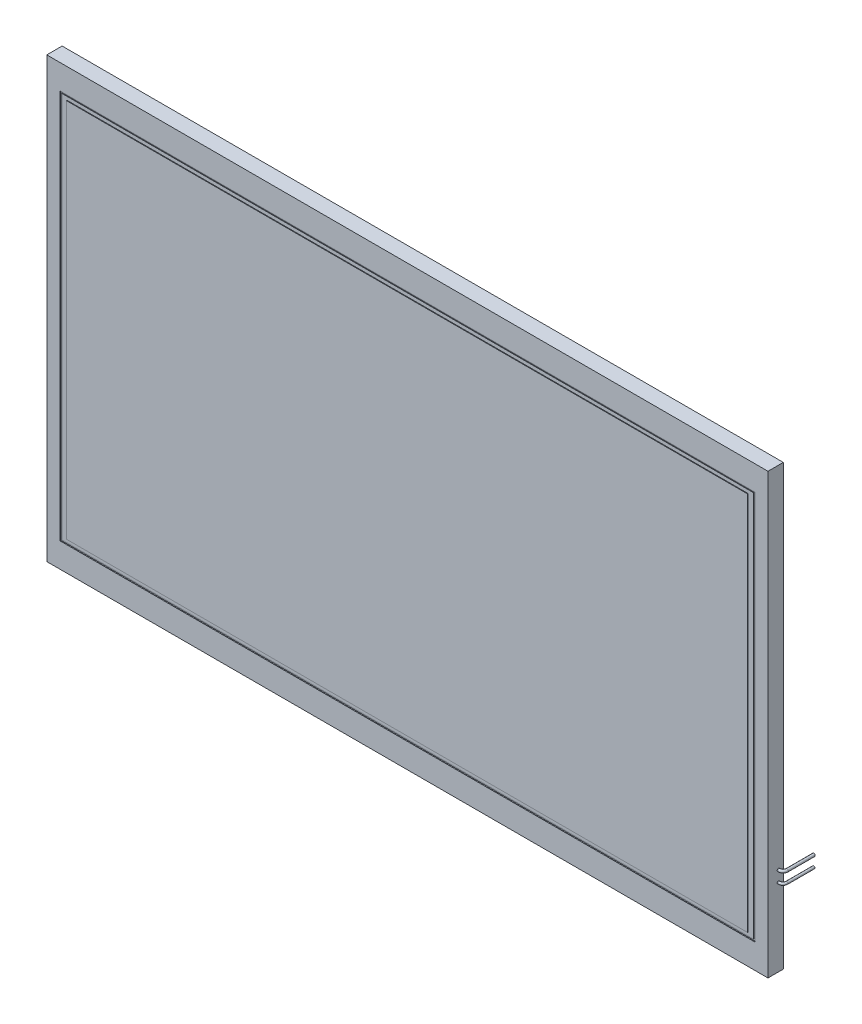
SolidWorks part; units mm, degrees
ref_plane "Front Plane" through (0, 0, 0) normal (0, 0, 1) x (1, 0, 0)
ref_plane "Top Plane" through (0, 0, 0) normal (0, 1, 0) x (1, 0, 0)
ref_plane "Right Plane" through (0, 0, 0) normal (1, 0, 0) x (0, 0, -1)
sketch "Sketch1" plane through (0, 0, 0) normal (0, 0, 1) x (1, 0, 0)
  line L1 (-117.5, -71.5) -> (117.5, -71.5)
  line L2 (-117.5, -71.5) -> (-117.5, 71.5)
  line L3 (-117.5, 71.5) -> (117.5, 71.5)
  line L4 (117.5, -71.5) -> (117.5, 71.5)
  line L5 (-117.5, -71.5) -> (117.5, 71.5) construction
  line L6 (-117.5, 71.5) -> (117.5, -71.5) construction
  point P0 (0, 0)
  dimension "D1" = 235
  dimension "D2" = 143
extrude "Boss-Extrude1" add sketch "Sketch1" against normal blind 5
sketch "Sketch2" plane through (0, 0, 0) normal (0, 0, 1) x (1, 0, 0)
  line L1 (-113.2, -63.49) -> (113.2, -63.49)
  line L2 (-113.2, -63.49) -> (-113.2, 63.49)
  line L3 (-113.2, 63.49) -> (113.2, 63.49)
  line L4 (113.2, -63.49) -> (113.2, 63.49)
  line L5 (-113.2, -63.49) -> (113.2, 63.49) construction
  line L6 (-113.2, 63.49) -> (113.2, -63.49) construction
  point P0 (0, 0)
  dimension "D1" = 226.4
  dimension "D2" = 126.98
extrude "Cut-Extrude1" cut sketch "Sketch2" against normal blind 0.3
sketch "Sketch3" plane through (0, 0, 0) normal (0, 0, 1) x (1, 0, 0)
  line L0 (113.2, 63.49) -> (-113.2, 63.49) construction
  line L1 (-112.7, -62.99) -> (112.7, -62.99)
  line L2 (-112.7, -62.99) -> (-112.7, 62.99)
  line L3 (-112.7, 62.99) -> (112.7, 62.99)
  line L4 (112.7, -62.99) -> (112.7, 62.99)
  line L5 (-112.7, -62.99) -> (112.7, 62.99) construction
  line L6 (-112.7, 62.99) -> (112.7, -62.99) construction
  line L7 (-113.2, 63.49) -> (-113.2, -63.49) construction
  line L8 (-110.95, 61.88) -> (-110.95, -61.88)
  line L9 (-110.95, 61.88) -> (110.95, 61.88)
  line L10 (110.95, 61.88) -> (110.95, -61.88)
  line L11 (110.95, -61.88) -> (-110.95, -61.88)
  point P0 (0, 0)
  dimension "D1" = 0.5
  dimension "D2" = 0.5
  dimension "D3" = 1.75
  dimension "D4" = 1.75
  dimension "D5" = 1.11
  dimension "D6" = 1.11
extrude "Boss-Extrude2" add sketch "Sketch3" along normal blind 0.2 from surface separate body contours L1 L4 L3 L2 L10 L11 L8 L9 region at (-112.4418, 0, 0) starting at face at (0, 0, -0.3)
sketch "Sketch4" plane through (0, 0, -0.3) normal (0, 0, 1) x (1, 0, 0)
  line L1 (-110.95, -61.88) -> (110.95, -61.88)
  line L2 (-110.95, -61.88) -> (-110.95, 61.88)
  line L3 (-110.95, 61.88) -> (110.95, 61.88)
  line L4 (110.95, -61.88) -> (110.95, 61.88)
  line L5 (-110.95, -61.88) -> (110.95, 61.88) construction
  line L6 (-110.95, 61.88) -> (110.95, -61.88) construction
  point P0 (0, 0)
extrude "Boss-Extrude3" add sketch "Sketch4" along normal blind 0.2 from surface starting at face at (0, 0, -0.1)
sketch "Sketch5" plane through (0, 0, 0) normal (1, 0, 0) x (0, 0, -1)
  line L0 (1.2, -71.5) -> (1.2, -72)
  line L1 (5, -71.5) -> (0, -71.5) construction
  line L2 (0, 71.5) -> (0, -71.5) construction
  line L3 (2.2, -73) -> (69.2, -73)
  line L4 (1.3, -71.5) -> (1.3, -72)
  line L5 (2.2, -72.9) -> (69.2, -72.9)
  line L6 (1.2, -71.5) -> (1.3, -71.5)
  line L7 (69.2, -72.9) -> (69.2, -73)
  arc A0 (1.2, -72) -> (2.2, -73) centre (2.2, -72) ccw
  arc A1 (1.3, -72) -> (2.2, -72.9) centre (2.2, -72) ccw
  point P9 (1.2, -73)
  dimension "D3" = 1
  dimension "D5" = 67
  dimension "D1" = 1.2
  dimension "D2" = 1.5
  dimension "D4" = 0.1
extrude "Boss-Extrude4" add sketch "Sketch5" along normal blind 19.63 and the other way blind 18.67
sketch "Sketch7" plane through (0, -73, 0) normal (0, -1, 0) x (1, 0, 0)
  line L0 (-18.67, -29.3) -> (-12.27, -36.43)
  line L1 (-18.67, -2.2) -> (-18.67, -69.2) construction
  line L2 (-18.67, -2.2) -> (19.63, -2.2) construction
  line L3 (-12.27, -36.43) -> (-12.27, -69.2)
  line L4 (-18.67, -69.2) -> (19.63, -69.2) construction
  line L5 (-12.27, -69.2) -> (-18.67, -69.2)
  line L6 (-18.67, -69.2) -> (-18.67, -29.3)
  line L7 (0.48, 11.0885) -> (0.48, -8.894) construction
  line L8 (19.63, -69.2) -> (19.63, -29.3)
  line L9 (13.23, -69.2) -> (19.63, -69.2)
  line L10 (13.23, -36.43) -> (13.23, -69.2)
  line L11 (19.63, -29.3) -> (13.23, -36.43)
  point P18 (0.48, -2.2)
  dimension "D1" = 27.1
  dimension "D2" = 6.4
  dimension "D3" = 7.13
extrude "Cut-Extrude2" cut sketch "Sketch7" against normal blind 4.2
sketch "Sketch9" plane through (0, -73, 0) normal (0, -1, 0) x (1, 0, 0)
  line L0 (-12.27, -63.2) -> (-12.27, -69.2)
  line L1 (-12.27, -69.2) -> (-12.27, -36.43) construction
  line L2 (-12.27, -69.2) -> (13.23, -69.2)
  line L3 (13.23, -69.2) -> (13.23, -63.2)
  line L4 (13.23, -36.43) -> (13.23, -69.2) construction
  line L5 (13.23, -63.2) -> (-12.27, -63.2)
  dimension "D1" = 6
extrude "Boss-Extrude5" add sketch "Sketch9" against normal blind 0.3
sketch "Sketch8" plane through (0, -73, 0) normal (0, -1, 0) x (1, 0, 0)
  line L0 (-11.92, -69.2) -> (-11.92, -65.4)
  line L1 (-12.27, -69.2) -> (13.23, -69.2) construction
  line L3 (-11.62, -65.4) -> (-11.62, -69.2)
  line L4 (-11.92, -69.2) -> (-11.62, -69.2)
  line L5 (-12.27, -69.2) -> (-12.27, -36.43) construction
  line L6 (-11.92, -65.4) -> (-11.62, -65.4)
  line L7 (-11.42, -65.4) -> (-11.12, -65.4)
  line L8 (-11.42, -69.2) -> (-11.42, -65.4)
  line L9 (-11.12, -65.4) -> (-11.12, -69.2)
  line L10 (-11.42, -69.2) -> (-11.12, -69.2)
  line L11 (-10.92, -65.4) -> (-10.62, -65.4)
  line L12 (-10.92, -69.2) -> (-10.92, -65.4)
  line L13 (-10.62, -65.4) -> (-10.62, -69.2)
  line L14 (-10.92, -69.2) -> (-10.62, -69.2)
  line L15 (-10.42, -65.4) -> (-10.12, -65.4)
  line L16 (-10.42, -69.2) -> (-10.42, -65.4)
  line L17 (-10.12, -65.4) -> (-10.12, -69.2)
  line L18 (-10.42, -69.2) -> (-10.12, -69.2)
  line L19 (-9.92, -65.4) -> (-9.62, -65.4)
  line L20 (-9.92, -69.2) -> (-9.92, -65.4)
  line L21 (-9.62, -65.4) -> (-9.62, -69.2)
  line L22 (-9.92, -69.2) -> (-9.62, -69.2)
  line L23 (-9.42, -65.4) -> (-9.12, -65.4)
  line L24 (-9.42, -69.2) -> (-9.42, -65.4)
  line L25 (-9.12, -65.4) -> (-9.12, -69.2)
  line L26 (-9.42, -69.2) -> (-9.12, -69.2)
  line L27 (-8.92, -65.4) -> (-8.62, -65.4)
  line L28 (-8.92, -69.2) -> (-8.92, -65.4)
  line L29 (-8.62, -65.4) -> (-8.62, -69.2)
  line L30 (-8.92, -69.2) -> (-8.62, -69.2)
  line L31 (-8.42, -65.4) -> (-8.12, -65.4)
  line L32 (-8.42, -69.2) -> (-8.42, -65.4)
  line L33 (-8.12, -65.4) -> (-8.12, -69.2)
  line L34 (-8.42, -69.2) -> (-8.12, -69.2)
  line L35 (-7.92, -65.4) -> (-7.62, -65.4)
  line L36 (-7.92, -69.2) -> (-7.92, -65.4)
  line L37 (-7.62, -65.4) -> (-7.62, -69.2)
  line L38 (-7.92, -69.2) -> (-7.62, -69.2)
  line L39 (-7.42, -65.4) -> (-7.12, -65.4)
  line L40 (-7.42, -69.2) -> (-7.42, -65.4)
  line L41 (-7.12, -65.4) -> (-7.12, -69.2)
  line L42 (-7.42, -69.2) -> (-7.12, -69.2)
  line L43 (-6.92, -65.4) -> (-6.62, -65.4)
  line L44 (-6.92, -69.2) -> (-6.92, -65.4)
  line L45 (-6.62, -65.4) -> (-6.62, -69.2)
  line L46 (-6.92, -69.2) -> (-6.62, -69.2)
  line L47 (-6.42, -65.4) -> (-6.12, -65.4)
  line L48 (-6.42, -69.2) -> (-6.42, -65.4)
  line L49 (-6.12, -65.4) -> (-6.12, -69.2)
  line L50 (-6.42, -69.2) -> (-6.12, -69.2)
  line L51 (-5.92, -65.4) -> (-5.62, -65.4)
  line L52 (-5.92, -69.2) -> (-5.92, -65.4)
  line L53 (-5.62, -65.4) -> (-5.62, -69.2)
  line L54 (-5.92, -69.2) -> (-5.62, -69.2)
  line L55 (-5.42, -65.4) -> (-5.12, -65.4)
  line L56 (-5.42, -69.2) -> (-5.42, -65.4)
  line L57 (-5.12, -65.4) -> (-5.12, -69.2)
  line L58 (-5.42, -69.2) -> (-5.12, -69.2)
  line L59 (-4.92, -65.4) -> (-4.62, -65.4)
  line L60 (-4.92, -69.2) -> (-4.92, -65.4)
  line L61 (-4.62, -65.4) -> (-4.62, -69.2)
  line L62 (-4.92, -69.2) -> (-4.62, -69.2)
  line L63 (-4.42, -65.4) -> (-4.12, -65.4)
  line L64 (-4.42, -69.2) -> (-4.42, -65.4)
  line L65 (-4.12, -65.4) -> (-4.12, -69.2)
  line L66 (-4.42, -69.2) -> (-4.12, -69.2)
  line L67 (-3.92, -65.4) -> (-3.62, -65.4)
  line L68 (-3.92, -69.2) -> (-3.92, -65.4)
  line L69 (-3.62, -65.4) -> (-3.62, -69.2)
  line L70 (-3.92, -69.2) -> (-3.62, -69.2)
  line L71 (-3.42, -65.4) -> (-3.12, -65.4)
  line L72 (-3.42, -69.2) -> (-3.42, -65.4)
  line L73 (-3.12, -65.4) -> (-3.12, -69.2)
  line L74 (-3.42, -69.2) -> (-3.12, -69.2)
  line L75 (-2.92, -65.4) -> (-2.62, -65.4)
  line L76 (-2.92, -69.2) -> (-2.92, -65.4)
  line L77 (-2.62, -65.4) -> (-2.62, -69.2)
  line L78 (-2.92, -69.2) -> (-2.62, -69.2)
  line L79 (-2.42, -65.4) -> (-2.12, -65.4)
  line L80 (-2.42, -69.2) -> (-2.42, -65.4)
  line L81 (-2.12, -65.4) -> (-2.12, -69.2)
  line L82 (-2.42, -69.2) -> (-2.12, -69.2)
  line L83 (-1.92, -65.4) -> (-1.62, -65.4)
  line L84 (-1.92, -69.2) -> (-1.92, -65.4)
  line L85 (-1.62, -65.4) -> (-1.62, -69.2)
  line L86 (-1.92, -69.2) -> (-1.62, -69.2)
  line L87 (-1.42, -65.4) -> (-1.12, -65.4)
  line L88 (-1.42, -69.2) -> (-1.42, -65.4)
  line L89 (-1.12, -65.4) -> (-1.12, -69.2)
  line L90 (-1.42, -69.2) -> (-1.12, -69.2)
  line L91 (-0.92, -65.4) -> (-0.62, -65.4)
  line L92 (-0.92, -69.2) -> (-0.92, -65.4)
  line L93 (-0.62, -65.4) -> (-0.62, -69.2)
  line L94 (-0.92, -69.2) -> (-0.62, -69.2)
  line L95 (-0.42, -65.4) -> (-0.12, -65.4)
  line L96 (-0.42, -69.2) -> (-0.42, -65.4)
  line L97 (-0.12, -65.4) -> (-0.12, -69.2)
  line L98 (-0.42, -69.2) -> (-0.12, -69.2)
  line L99 (0.08, -65.4) -> (0.38, -65.4)
  line L100 (0.08, -69.2) -> (0.08, -65.4)
  line L101 (0.38, -65.4) -> (0.38, -69.2)
  line L102 (0.08, -69.2) -> (0.38, -69.2)
  line L103 (0.58, -65.4) -> (0.88, -65.4)
  line L104 (0.58, -69.2) -> (0.58, -65.4)
  line L105 (0.88, -65.4) -> (0.88, -69.2)
  line L106 (0.58, -69.2) -> (0.88, -69.2)
  line L107 (1.08, -65.4) -> (1.38, -65.4)
  line L108 (1.08, -69.2) -> (1.08, -65.4)
  line L109 (1.38, -65.4) -> (1.38, -69.2)
  line L110 (1.08, -69.2) -> (1.38, -69.2)
  line L111 (1.58, -65.4) -> (1.88, -65.4)
  line L112 (1.58, -69.2) -> (1.58, -65.4)
  line L113 (1.88, -65.4) -> (1.88, -69.2)
  line L114 (1.58, -69.2) -> (1.88, -69.2)
  line L115 (2.08, -65.4) -> (2.38, -65.4)
  line L116 (2.08, -69.2) -> (2.08, -65.4)
  line L117 (2.38, -65.4) -> (2.38, -69.2)
  line L118 (2.08, -69.2) -> (2.38, -69.2)
  line L119 (2.58, -65.4) -> (2.88, -65.4)
  line L120 (2.58, -69.2) -> (2.58, -65.4)
  line L121 (2.88, -65.4) -> (2.88, -69.2)
  line L122 (2.58, -69.2) -> (2.88, -69.2)
  line L123 (3.08, -65.4) -> (3.38, -65.4)
  line L124 (3.08, -69.2) -> (3.08, -65.4)
  line L125 (3.38, -65.4) -> (3.38, -69.2)
  line L126 (3.08, -69.2) -> (3.38, -69.2)
  line L127 (3.58, -65.4) -> (3.88, -65.4)
  line L128 (3.58, -69.2) -> (3.58, -65.4)
  line L129 (3.88, -65.4) -> (3.88, -69.2)
  line L130 (3.58, -69.2) -> (3.88, -69.2)
  line L131 (4.08, -65.4) -> (4.38, -65.4)
  line L132 (4.08, -69.2) -> (4.08, -65.4)
  line L133 (4.38, -65.4) -> (4.38, -69.2)
  line L134 (4.08, -69.2) -> (4.38, -69.2)
  line L135 (4.58, -65.4) -> (4.88, -65.4)
  line L136 (4.58, -69.2) -> (4.58, -65.4)
  line L137 (4.88, -65.4) -> (4.88, -69.2)
  line L138 (4.58, -69.2) -> (4.88, -69.2)
  line L139 (5.08, -65.4) -> (5.38, -65.4)
  line L140 (5.08, -69.2) -> (5.08, -65.4)
  line L141 (5.38, -65.4) -> (5.38, -69.2)
  line L142 (5.08, -69.2) -> (5.38, -69.2)
  line L143 (5.58, -65.4) -> (5.88, -65.4)
  line L144 (5.58, -69.2) -> (5.58, -65.4)
  line L145 (5.88, -65.4) -> (5.88, -69.2)
  line L146 (5.58, -69.2) -> (5.88, -69.2)
  line L147 (6.08, -65.4) -> (6.38, -65.4)
  line L148 (6.08, -69.2) -> (6.08, -65.4)
  line L149 (6.38, -65.4) -> (6.38, -69.2)
  line L150 (6.08, -69.2) -> (6.38, -69.2)
  line L151 (6.58, -65.4) -> (6.88, -65.4)
  line L152 (6.58, -69.2) -> (6.58, -65.4)
  line L153 (6.88, -65.4) -> (6.88, -69.2)
  line L154 (6.58, -69.2) -> (6.88, -69.2)
  line L155 (7.08, -65.4) -> (7.38, -65.4)
  line L156 (7.08, -69.2) -> (7.08, -65.4)
  line L157 (7.38, -65.4) -> (7.38, -69.2)
  line L158 (7.08, -69.2) -> (7.38, -69.2)
  line L159 (7.58, -65.4) -> (7.88, -65.4)
  line L160 (7.58, -69.2) -> (7.58, -65.4)
  line L161 (7.88, -65.4) -> (7.88, -69.2)
  line L162 (7.58, -69.2) -> (7.88, -69.2)
  line L163 (8.08, -65.4) -> (8.38, -65.4)
  line L164 (8.08, -69.2) -> (8.08, -65.4)
  line L165 (8.38, -65.4) -> (8.38, -69.2)
  line L166 (8.08, -69.2) -> (8.38, -69.2)
  line L167 (8.58, -65.4) -> (8.88, -65.4)
  line L168 (8.58, -69.2) -> (8.58, -65.4)
  line L169 (8.88, -65.4) -> (8.88, -69.2)
  line L170 (8.58, -69.2) -> (8.88, -69.2)
  line L171 (9.08, -65.4) -> (9.38, -65.4)
  line L172 (9.08, -69.2) -> (9.08, -65.4)
  line L173 (9.38, -65.4) -> (9.38, -69.2)
  line L174 (9.08, -69.2) -> (9.38, -69.2)
  line L175 (9.58, -65.4) -> (9.88, -65.4)
  line L176 (9.58, -69.2) -> (9.58, -65.4)
  line L177 (9.88, -65.4) -> (9.88, -69.2)
  line L178 (9.58, -69.2) -> (9.88, -69.2)
  line L179 (10.08, -65.4) -> (10.38, -65.4)
  line L180 (10.08, -69.2) -> (10.08, -65.4)
  line L181 (10.38, -65.4) -> (10.38, -69.2)
  line L182 (10.08, -69.2) -> (10.38, -69.2)
  line L183 (10.58, -65.4) -> (10.88, -65.4)
  line L184 (10.58, -69.2) -> (10.58, -65.4)
  line L185 (10.88, -65.4) -> (10.88, -69.2)
  line L186 (10.58, -69.2) -> (10.88, -69.2)
  line L187 (11.08, -65.4) -> (11.38, -65.4)
  line L188 (11.08, -69.2) -> (11.08, -65.4)
  line L189 (11.38, -65.4) -> (11.38, -69.2)
  line L190 (11.08, -69.2) -> (11.38, -69.2)
  line L191 (11.58, -65.4) -> (11.88, -65.4)
  line L192 (11.58, -69.2) -> (11.58, -65.4)
  line L193 (11.88, -65.4) -> (11.88, -69.2)
  line L194 (11.58, -69.2) -> (11.88, -69.2)
  line L195 (12.08, -65.4) -> (12.38, -65.4)
  line L196 (12.08, -69.2) -> (12.08, -65.4)
  line L197 (12.38, -65.4) -> (12.38, -69.2)
  line L198 (12.08, -69.2) -> (12.38, -69.2)
  line L199 (12.58, -65.4) -> (12.88, -65.4)
  line L200 (12.58, -69.2) -> (12.58, -65.4)
  line L201 (12.88, -65.4) -> (12.88, -69.2)
  line L202 (12.58, -69.2) -> (12.88, -69.2)
  dimension "D1" = 0.3
  dimension "D2" = 3.8
  dimension "D3" = 0.35
  dimension "D4" = 50
  dimension "D5" = 0.2
extrude "Cut-Extrude3" cut sketch "Sketch8" against normal blind 0.01
sketch "Sketch10" plane through (0, 0, 0) normal (1, 0, 0) x (0, 0, -1)
  line L4 (69.2, -72.7) -> (69.2, -73) construction
  line L7 (2.2, -73) -> (29.3, -73) construction
  line L8 (29.3, -72.9) -> (2.2, -72.9) construction
  line L9 (1.3, -72) -> (1.3, -71.5) construction
  line L10 (1.2, -71.5) -> (1.2, -72) construction
  line L11 (1.3, -71.5) -> (1.2, -71.5) construction
  line L12 (2.2, -73) -> (69.2, -73)
  line L13 (69.2, -72.9) -> (2.2, -72.9)
  line L14 (1.3, -72) -> (1.3, -71.5)
  line L15 (1.2, -71.5) -> (1.2, -72)
  line L16 (1.3, -71.5) -> (1.2, -71.5)
  line L17 (36.43, -73) -> (29.3, -73) construction
  line L18 (69.2, -72.9) -> (69.2, -73)
  arc A2 (1.2, -72) -> (2.2, -73) centre (2.2, -72) ccw construction
  arc A3 (1.3, -72) -> (2.2, -72.9) centre (2.2, -72) ccw construction
  arc A4 (1.2, -72) -> (2.2, -73) centre (2.2, -72) ccw
  arc A5 (1.3, -72) -> (2.2, -72.9) centre (2.2, -72) ccw
extrude "Boss-Extrude7" add sketch "Sketch10" against normal blind 12.256 from offset 30 offset against normal yes
sketch "Sketch11" plane through (0, -73, 0) normal (0, -1, 0) x (1, 0, 0)
  line L1 (-42.256, -2.2) -> (-42.256, -69.2) construction
  line L2 (-39.056, -5.2) -> (-39.056, -69.2)
  line L3 (-42.256, -69.2) -> (-30, -69.2) construction
  line L4 (-39.056, -69.2) -> (-42.256, -69.2)
  line L5 (-42.256, -69.2) -> (-42.256, -3.7)
  line L6 (-36.128, -2.2) -> (-36.128, -9.484) construction
  line L7 (-42.256, -2.2) -> (-30, -2.2) construction
  line L10 (-42.256, -3.7) -> (-40.556, -3.7)
  line L11 (-42.256, -1.2) -> (-30, -1.2) construction
  line L12 (-30, -3.7) -> (-31.7, -3.7)
  line L13 (-30, -69.2) -> (-30, -3.7)
  line L14 (-33.2, -69.2) -> (-30, -69.2)
  line L15 (-33.2, -5.2) -> (-33.2, -69.2)
  arc A0 (-40.556, -3.7) -> (-39.056, -5.2) centre (-40.556, -5.2) cw
  arc A1 (-31.7, -3.7) -> (-33.2, -5.2) centre (-31.7, -5.2) ccw
  point P15 (-39.056, -3.7)
  point P24 (-33.2, -3.7)
  dimension "D2" = 1.5
  dimension "D1" = 3.2
  dimension "D3" = 2.5
extrude "Cut-Extrude4" cut sketch "Sketch11" against normal up to next
sketch3d "3DSketch1"
  line L0 (117.5, -71.5, -5) -> (117.5, -71.5, 0) construction
  line L1 (117.5, -71.5, 0) -> (117.5, 71.5, 0) construction
  line L2 (117.5, -46.2, -3.4) -> (117.75, -46.2, -3.4)
  line L3 (119, -46.2, -4.65) -> (119, -46.2, -13.4)
  arc A0 (117.75, -46.2, -3.4) -> (119, -46.2, -4.65) centre (117.75, -46.2, -4.65) ccw
  point P0 (117.5, -46.2, -3.4)
  point P11 (119, -46.2, -3.4)
  point P12 (117.75, -44.95, -4.65)
  dimension "D5" = 1.25
  dimension "D2" = 3.4
  dimension "D1" = 25.3
  dimension "D4" = 1.5
  dimension "D3" = 10
sweep "Sweep1" add path "3DSketch1" circular profile diameter 0.8 parameters "D3"=0.8
sketch3d "3DSketch2"
  line L0 (117.5, -71.5, 0) -> (117.5, 71.5, 0) construction
  line L1 (117.5, -42.7004, -3.45) -> (117.75, -42.7004, -3.45)
  line L2 (119, -42.7004, -4.7) -> (119, -42.7004, -13.45)
  line L4 (117.5, -71.5, -5) -> (117.5, -71.5, 0) construction
  arc A1 (117.75, -42.7004, -3.45) -> (119, -42.7004, -4.7) centre (117.75, -42.7004, -4.7) ccw
  point P0 (117.5, -42.7004, -3.45)
  point P11 (119, -42.7004, -3.45)
  point P12 (117.75, -41.4504, -4.7)
  dimension "D5" = 1.25
  dimension "D1" = 3.45
  dimension "D2" = 28.7996
  dimension "D3" = 10
  dimension "D4" = 1.5
sweep "Sweep7" add path "3DSketch2" circular profile diameter 0.9 parameters "D3"=0.9
